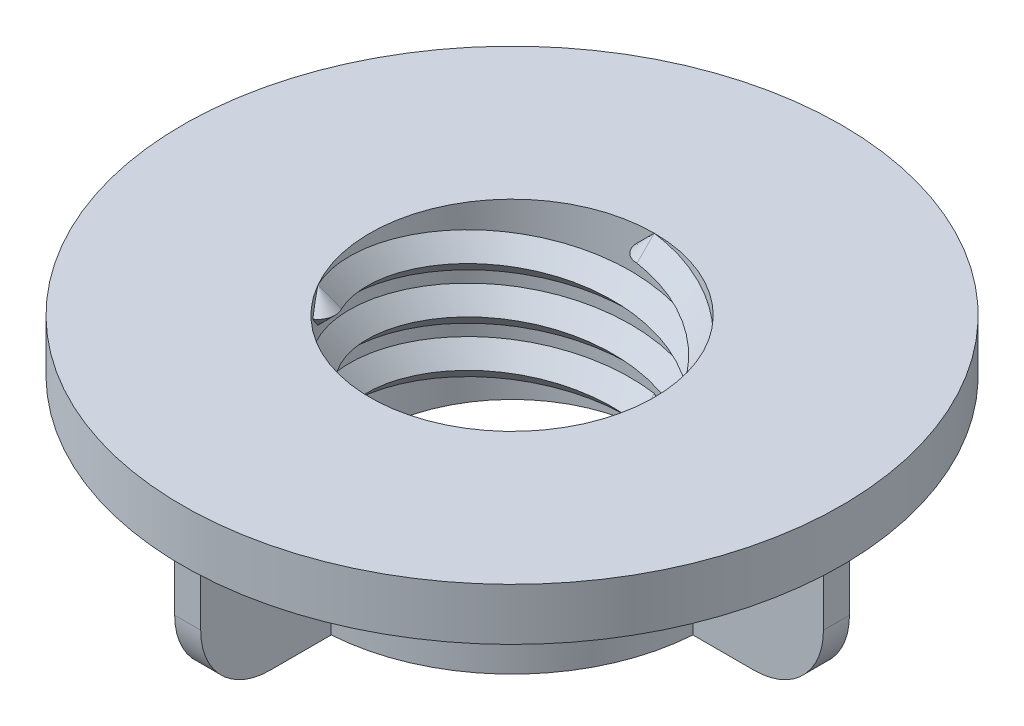
SolidWorks part; units mm, degrees
ref_plane "Front Plane" through (0, 0, 0) normal (0, 0, 1) x (1, 0, 0)
ref_plane "Top Plane" through (0, 0, 0) normal (0, 1, 0) x (1, 0, 0)
ref_plane "Right Plane" through (0, 0, 0) normal (1, 0, 0) x (0, 0, -1)
sketch "Sketch2" plane through (0, 0, 0) normal (0, 0, 1) x (1, 0, 0)
  line L0 (16.4, 0) -> (16.4, 20)
  line L1 (16.4, 20) -> (38, 20)
  line L2 (38, 20) -> (38, 14)
  line L3 (38, 14) -> (22.4, 14)
  line L4 (22.4, 14) -> (22.4, 0)
  line L5 (22.4, 0) -> (16.4, 0)
  line L6 (0, 0) -> (0, 55.2746) construction
  dimension "D1" = 6
  dimension "D2" = 6
  dimension "D3" = 32.8
  dimension "D4" = 76
  dimension "D5" = 20
revolve "Revolve1" add sketch "Sketch2" angle 360 about L6
sketch "Sketch3" plane through (0, 0, 0) normal (0, 0, 1) x (1, 0, 0)
  line L0 (-37.4, 14) -> (-37.4, 8)
  line L1 (-38, 14) -> (38, 14) construction
  line L2 (-29.4, 0) -> (-20.4, 0)
  line L3 (-22.4, 0) -> (22.4, 0) construction
  line L4 (-20.4, 0) -> (-20.4, 14)
  line L5 (-22.4, 14) -> (22.4, 14) construction
  line L6 (-37.4, 14) -> (-22.4, 14)
  line L7 (-22.4, 14) -> (-20.4, 14)
  arc A0 (-37.4, 8) -> (-29.4, 0) centre (-29.4, 8) ccw
  dimension "D3" = 8
  dimension "D1" = 2
  dimension "D2" = 15
extrude "Boss-Extrude1" add sketch "Sketch3" along normal mid plane 3
pattern_circular "CirPattern1" count 4 over 360 about axis through (0, 0, 0) along (0, -1, 0) of "Boss-Extrude1"
sketch "Sketch4" plane through (0, 0, 0) normal (0, -1, 0) x (1, 0, 0)
  circle A0 centre (0, 0) radius 16.4 construction
  circle A1 centre (0, 0) radius 16.4
curve "Helix/Spiral1" pitch 16 height 16 radius 16.4 centre (0, 0, 0) axis (0, 1, 0) start towards (0, 0, -1)
sketch "Sketch5" plane through (0, 0, 0) normal (1, 0, 0) x (0, 0, -1)
  line L0 (16.4, 0) -> (16.4, 4)
  line L1 (-16.4, 0) -> (16.4, 0) construction
  line L2 (16.4, 4) -> (14.4, 2)
  line L3 (14.4, 2) -> (16.4, 0)
  line L4 (0, 14) -> (0, 0) construction
  spline S0 degree 3 poles (16.4, 0) (16.4, 0.2948) (15.7271, 0.8896) (12.8209, 1.7776) (8.3682, 2.6667) (2.9063, 3.5555) (-2.9063, 4.4444) (-8.3682, 5.3333) (-12.8209, 6.2222) (-15.7271, 7.1111) (-16.7364, 8) (-15.7271, 8.8889) (-12.8209, 9.7778) (-8.3682, 10.6667) (-2.9063, 11.5556) (2.9063, 12.4445) (8.3682, 13.3333) (12.8209, 14.2224) (15.7271, 15.1104) (16.4, 15.7052) (16.4, 16) knots 0 0 0 0 0.055556 0.111111 0.166667 0.222222 0.277778 0.333333 0.388889 0.444444 0.5 0.555556 0.611111 0.666667 0.722222 0.777778 0.833333 0.888889 0.944444 1 1 1 1 construction
  dimension "D1" = 90
  dimension "D2" = 4
  dimension "D3" = 14.4
sweep "Sweep1" add profiles "Sketch5" path "Helix/Spiral1"
sketch "Sketch6" plane through (0, 0, 0) normal (1, 0, 0) x (0, 0, -1)
  line L3 (16.4, 0) -> (16.4, 4)
  line L4 (16.4, 4) -> (14.4, 2)
  line L5 (14.4, 2) -> (16.4, 0)
  line L6 (16.4, 0) -> (16.4, 4)
  line L7 (16.4, 4) -> (14.4, 2)
  line L8 (14.4, 2) -> (16.4, 0)
  dimension "D1" = 0
revolve "Revolve2" add sketch "Sketch6" angle 90 about L6
sketch "Sketch7" plane through (0, 0, 0) normal (-1, 0, 0) x (0, 0, 1)
  line L3 (-16.4, 20) -> (-16.4, 16)
  line L4 (-16.4, 16) -> (-14.4, 18)
  line L5 (-14.4, 18) -> (-16.4, 20)
  line L6 (-16.4, 20) -> (-16.4, 16)
  line L7 (-16.4, 16) -> (-14.4, 18)
  line L8 (-14.4, 18) -> (-16.4, 20)
  dimension "D1" = 0
revolve "Revolve3" add sketch "Sketch7" angle 90 about L6
pattern_circular "CirPattern2" count 3 over 360 about axis through (0, 0, 0) along (0, -1, 0) of "Revolve3", "Sweep1", "Revolve2"
